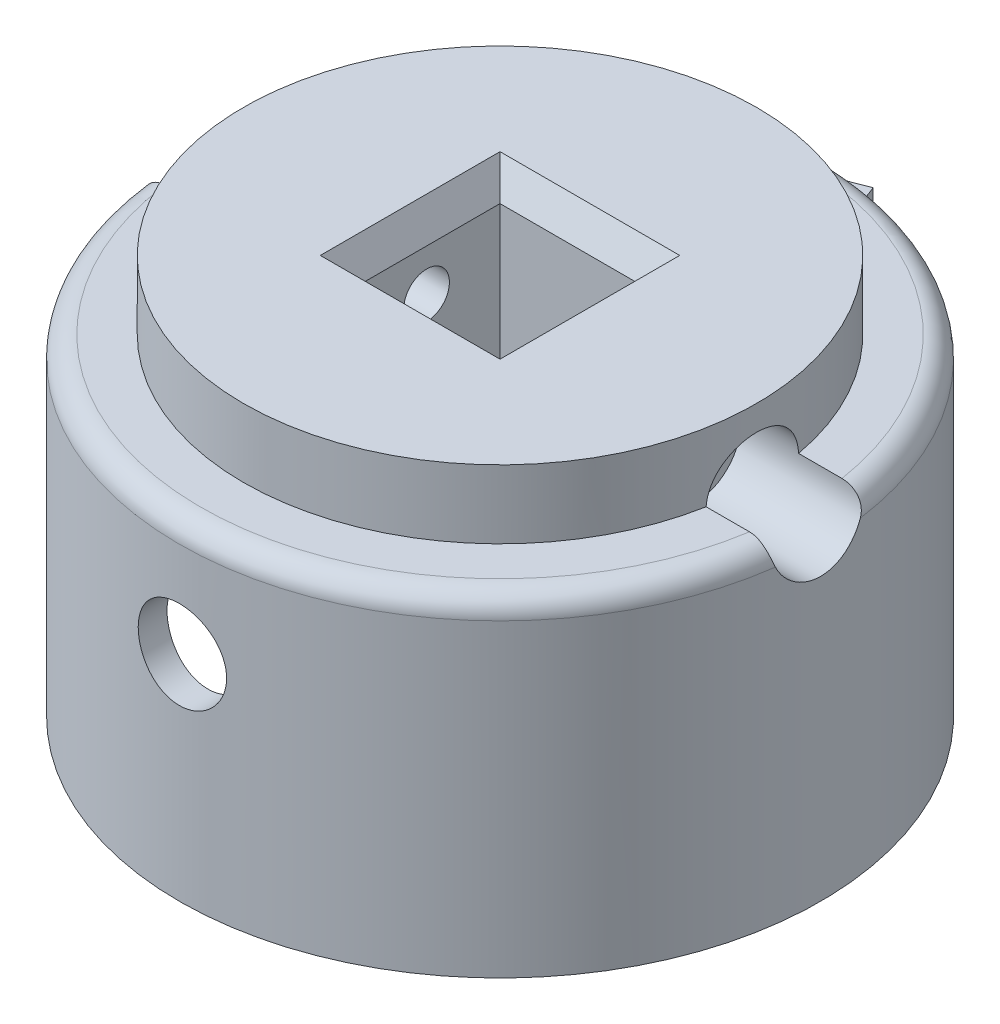
SolidWorks part; units mm, degrees
ref_plane "Спереди" through (0, 0, 0) normal (0, 0, 1) x (1, 0, 0)
ref_plane "Сверху" through (0, 0, 0) normal (0, 1, 0) x (1, 0, 0)
ref_plane "Справа" through (0, 0, 0) normal (1, 0, 0) x (0, 0, -1)
sketch "Sketch1" plane through (0, 0, 0) normal (0, 1, 0) x (1, 0, 0)
  circle A0 centre (0, 0) radius 22.5
  dimension "D1" = 45
extrude "Boss-Extrude1" add sketch "Sketch1" along normal blind 28
sketch "Sketch2" plane through (0, 0, 0) normal (0, -1, 0) x (1, 0, 0)
  line L1 (5.15, 5.15) -> (-5.15, 5.15)
  line L2 (5.15, 5.15) -> (5.15, -5.15)
  line L3 (5.15, -5.15) -> (-5.15, -5.15)
  line L4 (-5.15, 5.15) -> (-5.15, -5.15)
  line L5 (5.15, 5.15) -> (-5.15, -5.15) construction
  line L6 (5.15, -5.15) -> (-5.15, 5.15) construction
  point P0 (0, 0)
  dimension "D1" = 10.3
extrude "Cut-Extrude2" cut sketch "Sketch2" against normal through all
shell "Shell3" thickness 2 removed face at (0, 0, 0)
sketch "Sketch3" plane through (0, 0, 7.15) normal (0, 0, 1) x (1, 0, 0)
  line L0 (0, 26) -> (0, 0) construction
  line L1 (7.15, 26) -> (-7.15, 26) construction
  line L2 (7.15, 0) -> (-7.15, 0) construction
  line L3 (-22.5, 0) -> (22.5, 0) construction
  circle A0 centre (0, 15) radius 3.1
  dimension "D1" = 6.2
  dimension "D2" = 15
extrude "Cut-Extrude3" cut sketch "Sketch3" along normal through all
chamfer "Chamfer1" distance 2 angle 30 4 edges at (-5.15, 28, 0) (0, 28, 5.15) (5.15, 28, 0) (0, 28, -5.15) first distance on face at (-5.15, 14, 0) first distance on face at (0, 14, 5.15) first distance on face at (5.15, 14, 0) first distance on face at (0, 14, -5.15)
sketch "Sketch18" plane through (0, 26, 0) normal (0, -1, 0) x (1, 0, 0)
  line L0 (0, 0) -> (-18.4253, -8.9866) construction
  line L1 (0, 0) -> (-17.385, 10.8633) construction
  line L2 (0, 0) -> (0, -20.5) construction
  line L3 (-15.7289, -7.6715) -> (-18.4253, -8.9866)
  line L4 (-14.8408, 9.2736) -> (-17.385, 10.8633)
  circle A0 centre (0, 0) radius 20.5 construction
  arc A1 (-18.4253, -8.9866) -> (-17.385, 10.8633) centre (0, 0) cw
  arc A2 (-14.8408, 9.2736) -> (-15.7289, -7.6715) centre (0, 0) ccw
  dimension "D1" = 64
  dimension "D2" = 58
  dimension "D3" = 3
extrude "Boss-Extrude8" add sketch "Sketch18" along normal offset from surface (23 mm away) 3 up to face at (0, 0, 20.5)
sketch "Sketch9" plane through (0, 0, 0) normal (0, -1, 0) x (1, 0, 0)
  line L0 (0, -7.15) -> (0, -20.5) construction
  line L2 (2.0571, -22.4058) -> (-16.5967, -15.1921)
  line L3 (-16.5967, -15.1921) -> (-17.6788, -17.9902)
  line L4 (-17.6788, -17.9902) -> (0.975, -25.2038)
  line L5 (0.975, -25.2038) -> (2.0571, -22.4058)
  line L6 (-7.15, -7.15) -> (7.15, -7.15) construction
  line L7 (2.0571, -22.4058) -> (0, -7.15) construction
  circle A0 centre (0, 0) radius 22.5 construction
  circle A1 centre (0, 0) radius 20.5 construction
  dimension "D1" = 20
  dimension "D2" = 3
  dimension "D3" = 7.679
extrude "Boss-Extrude4" add sketch "Sketch9" against normal blind 20
sketch "Sketch11" plane through (0, 0, 0) normal (0, -1, 0) x (1, 0, 0)
  line L0 (2.0571, -22.4058) -> (7.15, -7.15)
  line L1 (7.15, -7.15) -> (-7.15, -7.15)
  line L2 (-7.15, -7.15) -> (-16.5967, -15.1921)
  line L3 (-16.5967, -15.1921) -> (2.0571, -22.4058) construction
  line L4 (-3.78, -20.1485) -> (-10.7596, -17.4494) construction
  arc A0 (2.0571, -22.4058) -> (-16.5967, -15.1921) centre (0, 0) ccw construction
  arc A1 (2.0571, -22.4058) -> (-16.5967, -15.1921) centre (0, 0) cw
  arc A2 (2.0571, -22.4058) -> (-16.5967, -15.1921) centre (0, 0) ccw construction
  point P4 (-7.2698, -18.7989)
extrude "Boss-Extrude6" add sketch "Sketch11" against normal up to surface (26 mm away) up to face at (0, 26, 0)
sketch "Sketch12" plane through (0, 0, 0) normal (0, -1, 0) x (1, 0, 0)
  line L0 (-7.15, -7.15) -> (-15.0727, -13.8947) construction
  line L1 (2.7554, -20.314) -> (7.15, -7.15) construction
  line L2 (3.8359, -17.0772) -> (2.7554, -20.314)
  line L3 (-15.0727, -13.8947) -> (-12.7884, -11.95)
  arc A0 (2.7554, -20.314) -> (-15.0727, -13.8947) centre (0, 0) cw
  arc A1 (-12.7884, -11.95) -> (3.8359, -17.0772) centre (0, 0) ccw
  arc A2 (2.7554, -20.314) -> (-15.0727, -13.8947) centre (0, 0) ccw construction
  dimension "D1" = 3
extrude "Cut-Extrude5" cut sketch "Sketch12" against normal blind 12
sketch "Sketch13" plane through (-8.3519, 0, -21.597) normal (-0.3607, 0, -0.9327) x (-0.9327, 0, 0.3607)
  line L0 (0, 20) -> (0, 0) construction
  line L1 (10, 20) -> (-10, 20) construction
  line L2 (10, 0) -> (-10, 0) construction
  circle A0 centre (0, 10) radius 3.8
  dimension "D1" = 7.6
extrude "Cut-Extrude6" cut sketch "Sketch13" against normal blind 16
sketch "Sketch15" plane through (-8.3519, 0, -21.597) normal (-0.3607, 0, -0.9327) x (-0.9327, 0, 0.3607)
  line L0 (-10, 10) -> (10, 10) construction
  line L1 (-10, 20) -> (-10, 0) construction
  line L2 (10, 20) -> (10, 0) construction
  line L4 (5, 11.5) -> (-5, 11.5)
  line L5 (5, 11.5) -> (5, 8.5)
  line L6 (5, 8.5) -> (-5, 8.5)
  line L7 (-5, 11.5) -> (-5, 8.5)
  line L8 (5, 11.5) -> (-5, 8.5) construction
  line L9 (5, 8.5) -> (-5, 11.5) construction
  point P6 (0, 10)
  dimension "D1" = 10
  dimension "D2" = 3
extrude "Cut-Extrude8" cut sketch "Sketch15" against normal blind 16
sketch "Sketch17" plane through (0, 0, 0) normal (0, -1, 0) x (1, 0, 0)
  line L0 (7.15, 7.15) -> (7.15, -7.15)
  line L1 (7.15, -7.15) -> (3.8359, -17.0772)
  line L2 (7.15, 7.15) -> (-7.15, 7.15)
  line L3 (-7.15, 7.15) -> (-7.15, -7.15)
  line L4 (-7.15, -7.15) -> (-12.7884, -11.95)
  arc A0 (3.8359, -17.0772) -> (-12.7884, -11.95) centre (0, 0) cw
  arc A1 (-12.7884, -11.95) -> (3.8359, -17.0772) centre (0, 0) ccw construction
extrude "Cut-Extrude9" cut sketch "Sketch17" against normal blind 2
sketch "Sketch20" plane through (0, 26, 0) normal (0, -1, 0) x (1, 0, 0)
  line L0 (2.7554, -20.314) -> (7.15, -7.15)
  line L1 (7.15, -7.15) -> (7.15, 7.15)
  line L2 (7.15, 7.15) -> (-7.15, 7.15)
  line L3 (-7.15, 7.15) -> (-7.15, -7.15)
  line L4 (-7.15, -7.15) -> (-15.0727, -13.8947)
  arc A0 (2.7554, -20.314) -> (-15.0727, -13.8947) centre (0, 0) ccw
  arc A1 (2.7554, -20.314) -> (-17.385, 10.8633) centre (0, 0) ccw construction
extrude "Boss-Extrude10" add sketch "Sketch20" along normal blind 7
sketch "Sketch21" plane through (0, 28, 0) normal (0, 1, 0) x (1, 0, 0)
  circle A0 centre (0, 0) radius 18
  dimension "D1" = 36
extrude "Cut-Extrude11" cut sketch "Sketch21" against normal blind 4.8 flip side to cut
sketch "Sketch22" plane through (5.15, 0, 0) normal (-1, 0, 0) x (0, 0, 1)
  line L0 (0, 26) -> (0, 2) construction
  line L1 (5.15, 26) -> (-5.15, 26) construction
  line L2 (-5.15, 2) -> (5.15, 2) construction
  line L3 (-6.3047, 28) -> (6.3047, 28) construction
  circle A0 centre (0, 23) radius 1.6
  point P10 (0, 28)
  dimension "D1" = 3.2
  dimension "D2" = 5
extrude "Cut-Extrude12" cut sketch "Sketch22" against normal through all both and the other way through all
sketch "Sketch24" plane through (5.15, 0, 0) normal (-1, 0, 0) x (0, 0, 1)
  circle A0 centre (0, 23) radius 3.25
  dimension "D1" = 6.5
extrude "Cut-Extrude13" cut sketch "Sketch24" against normal through all from offset 8.5 offset against normal yes
sketch "Sketch25" plane through (-5.15, 0, 0) normal (1, 0, 0) x (0, 0, -1)
  line L0 (-5.15, 26) -> (-5.15, 2) construction
  line L1 (0, 19.8936) -> (2.6903, 21.4468)
  line L2 (2.6903, 21.4468) -> (2.6903, 24.5532)
  line L3 (2.6903, 24.5532) -> (0, 26.1064)
  line L4 (0, 26.1064) -> (-2.6903, 24.5532)
  line L5 (-2.6903, 24.5532) -> (-2.6903, 21.4468)
  line L6 (-2.6903, 21.4468) -> (0, 19.8936)
  circle A0 centre (0, 23) radius 3.1064 construction
extrude "Cut-Extrude14" cut sketch "Sketch25" against normal through all from offset 8.5 offset against normal yes
fillet "Fillet1" radius 1.5 2 edges at (-0.2792, 23.2, 22.4983) (-0.2792, 23.2, -22.4983)
